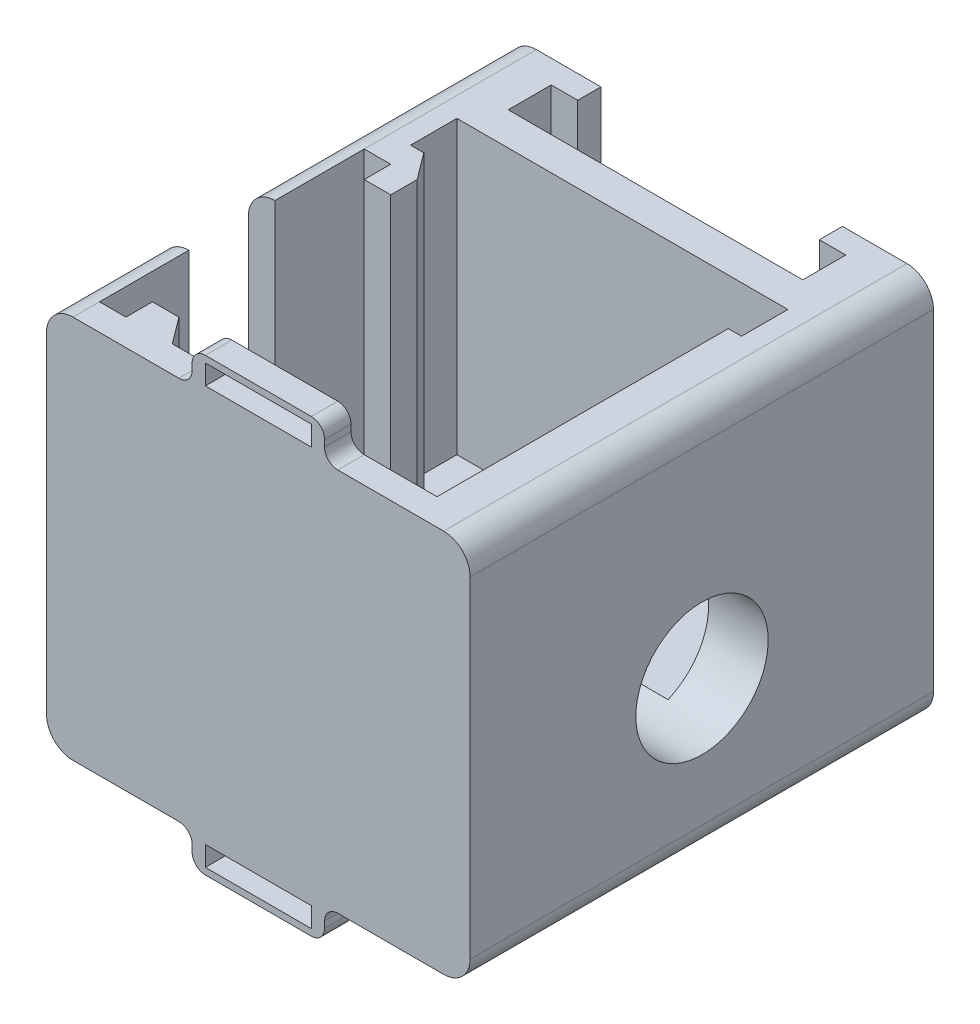
SolidWorks part; units mm, degrees
material "UNOBTANIUM"
ref_plane "Top Plane" through (0, 0, 0) normal (0, 0, 1) x (1, 0, 0)
ref_plane "Right Plane" through (0, 0, 0) normal (0, 1, 0) x (1, 0, 0)
ref_plane "Front Plane" through (0, 0, 0) normal (1, 0, 0) x (0, 0, -1)
ref_axis "x-axis" through (-17.6, 0, 0) along (1, 0, 0)
ref_axis "y-axis" through (0, -14.85, 0) along (0, 1, 0)
ref_axis "z-axis" through (0, 0, 36.75) along (0, 0, -1)
sketch "Sketch1" plane through (0, 0, 0) normal (0, 0, 1) x (1, 0, 0)
  line L1 (-16, 14.5) -> (16, 14.5)
  line L2 (-16, 14.5) -> (-16, -14.5)
  line L3 (-16, -14.5) -> (16, -14.5)
  line L4 (16, 14.5) -> (16, -14.5)
  line L5 (-16, 14.5) -> (16, -14.5) construction
  line L6 (-16, -14.5) -> (16, 14.5) construction
  point P0 (0, 0)
  dimension "D1" = 32
  dimension "D2" = 29
extrude "Boss-Extrude1" add sketch "Sketch1" along normal blind 35
fillet "Fillet1" radius 2 4 edges at (16, -14.5, 17.5) (16, 14.5, 17.5) (-16, -14.5, 17.5) (-16, 14.5, 17.5)
sketch "Sketch2" plane through (0, -14.5, 0) normal (0, -1, 0) x (1, 0, 0)
  line L0 (-9.125, 0) -> (-9.125, 1.75)
  line L1 (-14, 0) -> (14, 0) construction
  line L2 (-9.125, 1.75) -> (-11.125, 1.75)
  line L3 (-11.125, 1.75) -> (-11.125, 5)
  line L4 (-11.125, 5) -> (11.125, 5)
  line L5 (11.125, 5) -> (11.125, 1.75)
  line L6 (11.125, 1.75) -> (9.125, 1.75)
  line L7 (9.125, 1.75) -> (9.125, 0)
  line L9 (-9.125, 0) -> (9.125, 0)
  point P4 (0, 0)
  dimension "D1" = 18.25
  dimension "D2" = 1.75
  dimension "D3" = 3.25
  dimension "D4" = 22.25
extrude "Slot for Coil" cut sketch "Sketch2" against normal through all both and the other way through all
sketch "Sketch3" plane through (0, -14.5, 0) normal (0, -1, 0) x (1, 0, 0)
  line L0 (-9.125, 0) -> (-9.125, 1.75)
  line L1 (-9.125, 1.75) -> (-11.125, 1.75)
  line L2 (-11.125, 1.75) -> (-11.125, 5)
  line L3 (-11.125, 5) -> (11.125, 5)
  line L4 (11.125, 5) -> (11.125, 1.75)
  line L5 (11.125, 1.75) -> (9.125, 1.75)
  line L6 (9.125, 1.75) -> (9.125, 0)
  line L7 (9.125, 0) -> (-9.125, 0)
extrude "Boss-Extrude2" add sketch "Sketch3" against normal blind 7
sketch "Sketch4" plane through (0, 0, 1.75) normal (0, 0, -1) x (-1, 0, 0)
  line L1 (-9.125, 7.5) -> (-9.125, 6.5)
  line L2 (-9.125, 14.5) -> (-9.125, -7.5) construction
  arc A0 (-9.125, 7.5) -> (-9.125, 6.5) centre (-9.5, 7) cw
  dimension "D1" = 0.625
  dimension "D2" = 0.25
  dimension "D3" = 7
extrude "Boss-Extrude3" add sketch "Sketch4" along normal up to surface (1.75 mm away) up to face at (0, 1.1667, 0)
mirror "Mirror1" about plane through (0, 0, 0) normal (1, 0, 0) of "Boss-Extrude3"
sketch "Sketch5" plane through (0, 0, 0) normal (0, 0, -1) x (-1, 0, 0)
  line L0 (9.125, -7.5) -> (-9.125, -7.5) construction
  line L1 (-1, -7.5) -> (1, -7.5)
  line L2 (-1, -7.5) -> (-1, -14.5)
  line L3 (-1, -14.5) -> (1, -14.5)
  line L4 (1, -7.5) -> (1, -14.5)
  line L5 (14, -14.5) -> (-14, -14.5) construction
  point P8 (0, -7.5)
  dimension "D1" = 2
extrude "Cut-Extrude2" cut sketch "Sketch5" against normal offset from surface (33 mm away) 2 up to face at (0, 0, 35)
sketch "Sketch6" plane through (0, 14.5, 0) normal (0, 1, 0) x (1, 0, 0)
  line L0 (-12.5, -7.5) -> (-12.5, -11)
  line L1 (-12.5, -11) -> (-11.5, -11)
  line L2 (-11.5, -11) -> (-11.5, -33)
  line L3 (-11.5, -33) -> (11.5, -33)
  line L4 (11.5, -33) -> (11.5, -11)
  line L5 (11.5, -11) -> (12.5, -11)
  line L6 (12.5, -11) -> (12.5, -7.5)
  line L7 (12.5, -7.5) -> (-12.5, -7.5)
  line L8 (11.125, -5) -> (-11.125, -5) construction
  line L9 (0, -7.5) -> (0, -5) construction
  line L10 (14, -35) -> (-14, -35) construction
  dimension "D1" = 2.5
  dimension "D2" = 3.5
  dimension "D3" = 1
  dimension "D4" = 25
  dimension "D5" = 2
extrude "Cut-Extrude3" cut sketch "Sketch6" against normal up to surface (22 mm away) up to face at (7.0833, -7.5, 2.25)
sketch "Sketch7" plane through (0, -14.5, 0) normal (0, -1, 0) x (1, 0, 0)
  line L0 (1, 0) -> (14, 0) construction
  line L1 (1, 0) -> (-1, 0)
  line L2 (1, 0) -> (1, 33)
  line L3 (1, 33) -> (-1, 33)
  line L4 (-1, 0) -> (-1, 33)
  line L5 (1, 33) -> (1, 0) construction
extrude "Boss-Extrude4" add sketch "Sketch7" against normal blind 0.25
fillet "Fillet2" radius 6 1 edges at (0, -14.25, 33)
ref_axis "Axis1" through (63.07, 0, 17.75) along (-1, 0, 0)
ref_plane "Plane1" through (0, 0, 17.75) normal (0, 0, -1) x (-1, 0, 0)
sketch "Sketch9" plane through (0, 0, 17.75) normal (0, 0, -1) x (-1, 0, 0)
  line L0 (-15, 6) -> (-14, 6)
  line L1 (-16, -12.5) -> (-16, 12.5) construction
  line L2 (-14, 6) -> (-14, 3.325)
  line L3 (-14, 3.325) -> (-11.5, 3.325)
  line L4 (-11.5, 3.325) -> (-11.5, 0)
  line L5 (-63.07, 0) -> (46.93, 0) construction
  line L6 (-11.5, 0) -> (-16, 0)
  line L8 (-16, 0) -> (0, 0) construction
  line L9 (-11.5, -7.5) -> (-11.5, 14.5) construction
  line L10 (-15, 6) -> (-15, 5)
  line L11 (-15, 5) -> (-16, 5)
  line L12 (-16, 5) -> (-16, 0)
  point P4 (0.0866, 0)
  point P15 (0, 0)
  point P16 (0, 0)
  dimension "D1" = 6.65
  dimension "D2" = 12
  dimension "D3" = 1
  dimension "D4" = 1
  dimension "D5" = 10
revolve "Cut-Revolve1" [suppressed] cut sketch "Sketch9" angle 360 about L8
sketch "Sketch10" plane through (0, 14.5, 0) normal (0, 1, 0) x (1, 0, 0)
  line L0 (11.5, -31) -> (13.5, -31)
  line L1 (11.5, -11) -> (11.5, -33) construction
  line L2 (13.5, -31) -> (13.5, -33)
  line L3 (13.5, -33) -> (11.5, -33)
  line L4 (11.5, -33) -> (11.5, -31)
  dimension "D1" = 2
  dimension "D2" = 2
extrude "Cut-Extrude4" [suppressed] cut sketch "Sketch10" against normal up to surface (20 mm away)
mirror "Mirror2" [suppressed] about plane through (0, 0, 0) normal (1, 0, 0)
sketch "Sketch11" plane through (-16, 0, 44) normal (1, 0, 0) x (0, 0, -1)
  line L0 (21, 25) -> (21, 0) construction
  line L4 (24.25, 25) -> (24.25, 0)
  line L5 (17.75, 25) -> (17.75, 0)
  line L6 (9, 12.5) -> (44, 12.5) construction
  line L7 (21, 0) -> (44, 0) construction
  line L8 (9, 12.5) -> (9, -12.5) construction
  arc A2 (24.25, 25) -> (17.75, 25) centre (21, 25) ccw
  arc A3 (17.75, 0) -> (24.25, 0) centre (21, 0) ccw
  point P2 (21, 12.5)
  dimension "D1" = 6.5
  dimension "D2" = 12
extrude "Cut-Extrude5" cut sketch "Sketch11" along normal up to surface (4.5 mm away) up to face at (-11.5, 3.5, 22)
sketch "Sketch14" plane through (0, 14.5, 0) normal (0, 1, 0) x (1, 0, 0)
  line L0 (-11.5, -11) -> (-11.5, -19.75) construction
  line L1 (-11.5, -13) -> (-14, -13)
  line L2 (-11.5, -13) -> (-11.5, -33)
  line L3 (-11.5, -33) -> (-14, -33)
  line L4 (-14, -13) -> (-14, -33)
  line L5 (-16, -35) -> (-16, -26.25) construction
  line L6 (-11.5, -26.25) -> (-11.5, -19.75) construction
  point P12 (-11.5, -23)
  dimension "D1" = 2
extrude "Cut-Extrude6" cut sketch "Sketch14" against normal up to surface (22 mm away) up to face at (-8.3333, -7.5, 17.1667)
sketch "Sketch16" plane through (0, 14.5, 0) normal (0, 1, 0) x (1, 0, 0)
  line L1 (-12, -13) -> (-10, -13)
  line L2 (-12, -13) -> (-12, -15)
  line L3 (-12, -15) -> (-10, -15)
  line L4 (-10, -13) -> (-10, -15)
  line L5 (-14, -33) -> (-14, -13) construction
  line L6 (-12, -33) -> (-12, -31)
  line L7 (-14, -33) -> (11.5, -33) construction
  line L8 (-12, -31) -> (-10, -31)
  line L9 (-10, -31) -> (-10, -33)
  line L10 (-10, -33) -> (-12, -33)
  line L11 (-12.5, -11) -> (-11.5, -11) construction
  line L13 (-11.5, -13) -> (-14, -13) construction
  line L14 (-14, -13) -> (-14, -19.75) construction
  dimension "D1" = 4
  dimension "D2" = 2
  dimension "D3" = 2
  dimension "D4" = 2
  dimension "D5" = 2
extrude "Boss-Extrude5" add sketch "Sketch16" against normal up to surface (22 mm away) up to face at (-9.75, -7.5, 16.125)
sketch "Sketch20" plane through (0, 14.5, 0) normal (0, 1, 0) x (1, 0, 0)
  line L0 (-11.5, -11) -> (-10, -13)
  line L1 (-10, -13) -> (-11.5, -13)
  line L2 (-11.5, -13) -> (-11.5, -11)
  line L3 (-10, -31) -> (-8.5, -33)
  line L4 (-1, -33) -> (-10, -33) construction
  line L5 (-8.5, -33) -> (-10, -33)
  line L6 (-10, -33) -> (-10, -31)
extrude "Boss-Extrude6" add sketch "Sketch20" against normal up to surface (22 mm away) up to face at (-10.375, -7.5, 19.5625)
sketch "Sketch21" plane through (0, 14.5, 0) normal (0, 1, 0) x (-1, 0, 0)
  line L0 (0, 0) -> (0, 35) construction
  line L1 (-14, 35) -> (14, 35) construction
  line L2 (8.5, 33) -> (-11.5, 33) construction
  line L3 (-5, 35) -> (5, 35)
  line L4 (-5, 35) -> (-5, 33)
  line L5 (-5, 33) -> (5, 33)
  line L6 (5, 35) -> (5, 33)
  point P12 (0, 35)
  dimension "D1" = 10
extrude "Boss-Extrude7" add sketch "Sketch21" along normal blind 2.5
sketch "Sketch23" plane through (0, 0, 35) normal (0, 0, 1) x (1, 0, 0)
  line L0 (0, 0) -> (0, 17) construction
  line L3 (-4, 16.5) -> (4, 16.5)
  line L4 (-4, 16.5) -> (-4, 15)
  line L5 (-4, 15) -> (4, 15)
  line L6 (4, 16.5) -> (4, 15)
  line L7 (-5, 17) -> (5, 17) construction
  point P3 (0, 16.5)
  dimension "D1" = 1.5
  dimension "D2" = 8
  dimension "D3" = 0.5
extrude "Cut-Extrude7" cut sketch "Sketch23" against normal up to next
mirror "Mirror3" about plane through (0, 0, 0) normal (0, 1, 0) of "Boss-Extrude7", "Cut-Extrude7"
fillet "Fillet3" radius 1 8 edges at (-5, 14.5, 34) (5, 14.5, 34) (5, 17, 34) (-5, 17, 34) (5, -14.5, 34) (-5, -14.5, 34) (5, -17, 34) (-5, -17, 34)
sketch "Sketch26" plane through (16, 0, 0) normal (1, 0, 0) x (0, 0, -1)
  circle A0 centre (-17.485, -2.89) radius 5
  point P2 (-17.485, -2.89)
  dimension "D1" = 10
extrude "Cut-Extrude8" cut sketch "Sketch26" against normal up to next
